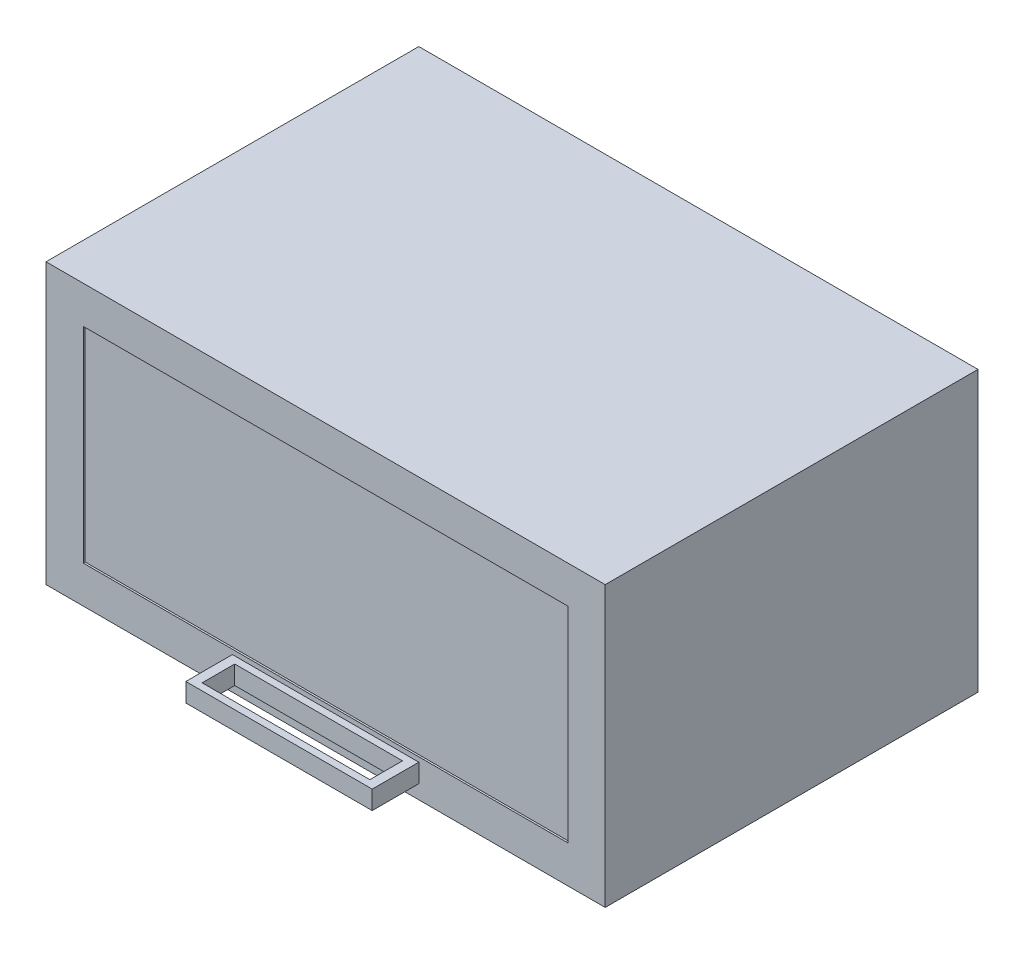
SolidWorks part; units mm, degrees
ref_plane "Спереди" through (0, 0, 0) normal (0, 0, 1) x (1, 0, 0)
ref_plane "Сверху" through (0, 0, 0) normal (0, 1, 0) x (1, 0, 0)
ref_plane "Справа" through (0, 0, 0) normal (1, 0, 0) x (0, 0, -1)
sketch "Эскиз1" plane through (0, 0, 0) normal (0, 1, 0) x (1, 0, 0)
  line L1 (0, 0) -> (-600, 0)
  line L2 (0, 0) -> (0, -400)
  line L3 (0, -400) -> (-600, -400)
  line L4 (-600, 0) -> (-600, -400)
  dimension "D1" = 600
  dimension "D2" = 400
extrude "Бобышка-Вытянуть1" add sketch "Эскиз1" along normal blind 300
sketch "Эскиз2" plane through (0, 0, 400) normal (0, 0, 1) x (1, 0, 0)
  line L1 (-400, 35) -> (-200, 35)
  line L2 (-400, 35) -> (-400, 15)
  line L3 (-400, 15) -> (-200, 15)
  line L4 (-200, 35) -> (-200, 15)
  line L5 (-600, 0) -> (0, 0) construction
  point P4 (-300, 15)
  point P7 (-300, 0)
  dimension "D1" = 200
  dimension "D2" = 15
  dimension "D3" = 20
extrude "Бобышка-Вытянуть2" add sketch "Эскиз2" along normal blind 50
sketch "Эскиз3" plane through (0, 35, 0) normal (0, 1, 0) x (1, 0, 0)
  line L0 (-400, -450) -> (-400, -400) construction
  line L1 (-390, -407.5) -> (-210, -407.5)
  line L2 (-390, -407.5) -> (-390, -442.5)
  line L3 (-390, -442.5) -> (-210, -442.5)
  line L4 (-210, -407.5) -> (-210, -442.5)
  line L5 (-200, -450) -> (-400, -450) construction
  point P6 (-400, -425)
  point P7 (-390, -425)
  point P8 (-300, -442.5)
  point P11 (-300, -450)
  dimension "D1" = 180
  dimension "D2" = 35
extrude "Вырез-Вытянуть1" cut sketch "Эскиз3" against normal blind 50
sketch "Эскиз4" plane through (0, 0, 400) normal (0, 0, 1) x (1, 0, 0)
  line L0 (-600, 300) -> (0, 300) construction
  line L1 (-560, 260) -> (-40, 260)
  line L2 (-560, 260) -> (-560, 40)
  line L3 (-560, 40) -> (-40, 40)
  line L4 (-40, 260) -> (-40, 40)
  line L5 (-600, 300) -> (-600, 0) construction
  point P4 (-300, 260)
  point P7 (-300, 300)
  point P8 (-560, 150)
  point P11 (-600, 150)
  dimension "D1" = 40
  dimension "D2" = 40
extrude "Вырез-Вытянуть2" cut sketch "Эскиз4" against normal blind 2
